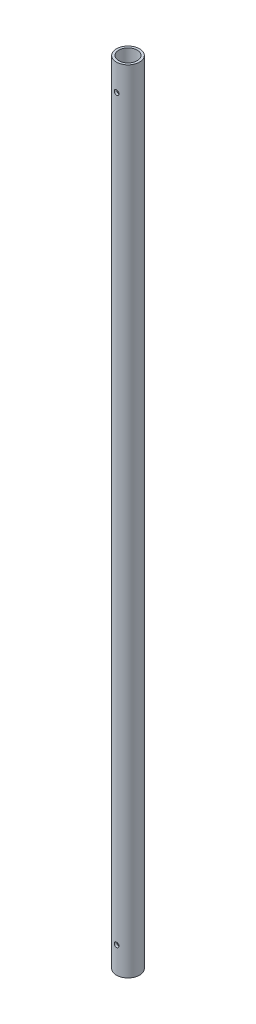
SolidWorks part; units mm, degrees
ref_plane "Front Plane" through (0, 0, 0) normal (0, 0, 1) x (1, 0, 0)
ref_plane "Top Plane" through (0, 0, 0) normal (0, 1, 0) x (1, 0, 0)
ref_plane "Right Plane" through (0, 0, 0) normal (1, 0, 0) x (0, 0, -1)
sketch "Sketch1" plane through (0, 0, 0) normal (0, 1, 0) x (1, 0, 0)
  circle A0 centre (0, 0) radius 16.7005
  point P0 (0, 0)
  dimension "D3" = 33.401
extrude "Boss-Extrude1" add sketch "Sketch1" along normal blind 1143
sketch "Sketch2" plane through (0, 0, 0) normal (0, 0, 1) x (1, 0, 0)
  line L3 (16.7005, 1143) -> (-16.7005, 1143) construction
  line L5 (-16.7005, 0) -> (16.7005, 0) construction
  circle A0 centre (0, 38.1) radius 3.429
  circle A1 centre (0, 1104.9) radius 3.429
  dimension "D3" = 6.858
  dimension "D1" = 38.1
  dimension "D4" = 38.1
extrude "Cut-Extrude1" cut sketch "Sketch2" along normal blind 25.4 and the other way blind 25.4
sketch "Sketch3" plane through (0, 0, 0) normal (0, -1, 0) x (1, 0, 0)
  circle A2 centre (0, 0) radius 13.3223
  circle A3 centre (0, 0) radius 13.3223
  dimension "D1" = 3.3782
extrude "Cut-Extrude2" cut sketch "Sketch3" against normal through all
